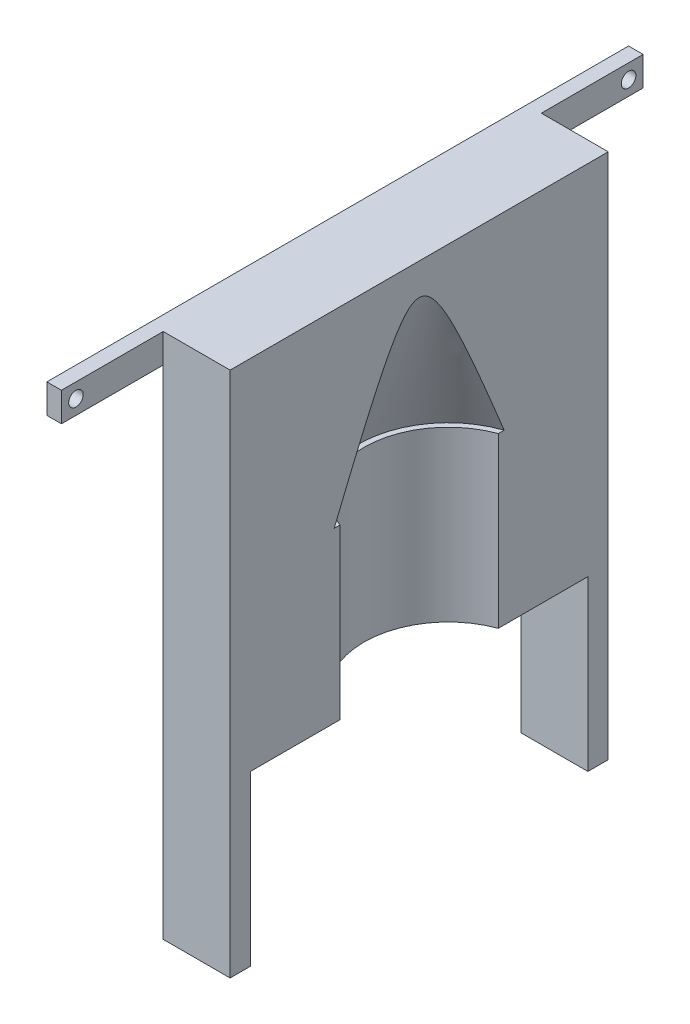
SolidWorks part; units mm, degrees
ref_plane "Plan de face" through (0, 0, 0) normal (0, 0, 1) x (1, 0, 0)
ref_plane "Plan de dessus" through (0, 0, 0) normal (0, 1, 0) x (1, 0, 0)
ref_plane "Plan de droite" through (0, 0, 0) normal (1, 0, 0) x (0, 0, -1)
sketch "Esquisse1" plane through (0, 0, 0) normal (1, 0, 0) x (0, 0, -1)
  line L1 (65, 90.5) -> (-65, 90.5)
  line L2 (65, 90.5) -> (65, -90.5)
  line L3 (65, -90.5) -> (-65, -90.5)
  line L4 (-65, 90.5) -> (-65, -90.5)
  line L5 (65, 90.5) -> (-65, -90.5) construction
  line L6 (65, -90.5) -> (-65, 90.5) construction
  point P0 (0, 0)
  dimension "D1" = 181
  dimension "D2" = 130
extrude "BASE" add sketch "Esquisse1" along normal blind 23
sketch "Esquisse2" plane through (23, 0, 0) normal (1, 0, 0) x (0, 0, -1)
  line L0 (-65, -90.5) -> (65, -90.5) construction
  line L1 (58, -32.5) -> (-58, -32.5)
  line L2 (58, -32.5) -> (58, -90.5)
  line L3 (58, -90.5) -> (-58, -90.5)
  line L4 (-58, -32.5) -> (-58, -90.5)
  line L5 (58, -32.5) -> (-58, -90.5) construction
  line L6 (58, -90.5) -> (-58, -32.5) construction
  line L7 (0, 0) -> (0, -90.5) construction
  point P0 (0, -61.5)
  dimension "D1" = 58
  dimension "D2" = 116
extrude "VIDE CUBE" cut sketch "Esquisse2" against normal through all
ref_plane "MILEUX OBJECT" through (33, 0, 0) normal (1, 0, 0) x (0, 0, -1)
sketch "Esquisse3" plane through (0, -32.5, 0) normal (0, -1, 0) x (1, 0, 0)
  line L0 (33, -66) -> (33, 66) construction
  circle A0 centre (33, 0) radius 29
  dimension "D1" = 58
extrude "VIDE CYLINDRE" cut sketch "Esquisse3" against normal blind 58
ref_axis "AXE CYLINDRE CONE" through (33, 119.5564, 0) along (0, -1, 0)
sketch "Esquisse4" plane through (33, 0, 0) normal (1, 0, 0) x (0, 0, -1)
  line L0 (0, 25.5) -> (30.8832, 25.5)
  line L1 (-27.2213, 25.5) -> (27.2213, 25.5) construction
  line L2 (30.8832, 25.5) -> (0, 105.5)
  line L3 (0, 119.5564) -> (0, -167.1593) construction
  line L4 (0, 105.5) -> (0, 25.5)
  dimension "D1" = 80
  dimension "D2" = 30.8832
revolve "VIDE CONE" cut sketch "Esquisse4" angle 360 about L4
sketch "Esquisse5" plane through (0, 90.5, 0) normal (0, 1, 0) x (1, 0, 0)
  line L0 (0, 0) -> (0, -90) construction
  line L2 (-5, 90) -> (-5, -90) construction
  line L3 (-5, 100) -> (0, 100)
  line L4 (-5, 100) -> (-5, -100)
  line L5 (0, 0) -> (-10, 0) construction
  line L6 (-10, 100) -> (-10, -100) construction
  line L7 (-5, -100) -> (0, -100)
  line L8 (0, 100) -> (0, -100)
  point P3 (0, 0)
  point P7 (-5, 0)
  dimension "D2" = 5
  dimension "D3" = 200
  dimension "D4" = 5
extrude "FIXATION TIGE" add sketch "Esquisse5" against normal blind 10
sketch "Esquisse6" plane through (0, 0, 0) normal (1, 0, 0) x (0, 0, -1)
  line L0 (-100, 85.5) -> (-89.7155, 85.5) construction
  line L1 (-100, 80.5) -> (-100, 90.5) construction
  line L2 (0, -9.5234) -> (0, 137.602) construction
  line L3 (0, 119.5564) -> (0, -167.1593) construction
  line L4 (100, 85.5) -> (89.7155, 85.5) construction
  circle A0 centre (-95, 85.5) radius 2.5
  circle A1 centre (95, 85.5) radius 2.5
  dimension "D1" = 5
  dimension "D2" = 5
extrude "Enlèv. mat.-Extru.1" cut sketch "Esquisse6" against normal through all
